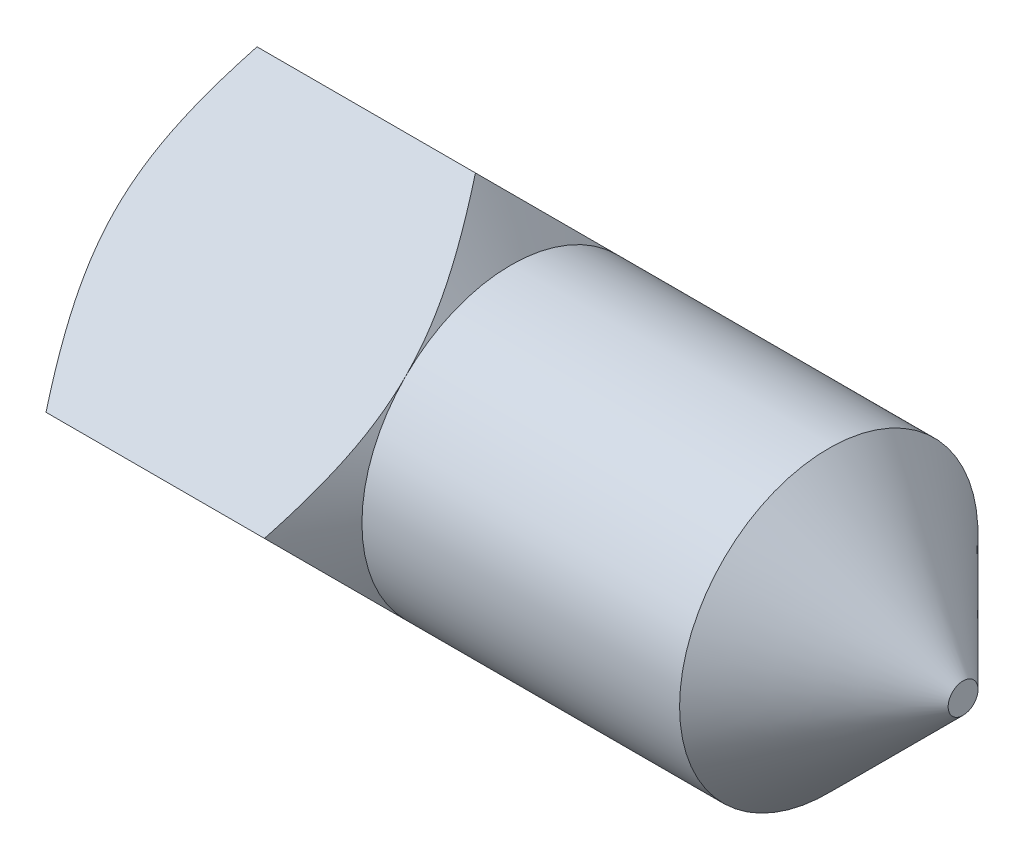
SolidWorks part; units mm, degrees
ref_plane "Front Plane" through (0, 0, 0) normal (0, 0, 1) x (1, 0, 0)
ref_plane "Top Plane" through (0, 0, 0) normal (0, 1, 0) x (1, 0, 0)
ref_plane "Right Plane" through (0, 0, 0) normal (1, 0, 0) x (0, 0, -1)
sketch "BaseHeadSke" plane through (0, 0, 0) normal (1, 0, 0) x (0, 0, -1)
  line L0 (0, 0) -> (14.1701, 0) construction
  line L1 (0, 0) -> (0, 11.9761) construction
  line L2 (0, 2.8284) -> (2.8284, 0)
  line L3 (0, -2.8284) -> (2.8284, 0)
  line L4 (0, 2.8284) -> (-2.8284, 0)
  line L5 (0, -2.8284) -> (-2.8284, 0)
  dimension "D1" = 45
  dimension "Width_flats" = 4
extrude "BaseHead" add sketch "BaseHeadSke" along normal blind 4
sketch "HeadChamferSke" plane through (0, 0, 0) normal (0, 0, 1) x (1, 0, 0)
  line L0 (0, 0) -> (6.1973, 0) construction
  line L1 (2, 2.8284) -> (2, -3.5627) construction
  line L2 (4, 2.8284) -> (0, 2.8284) construction
  line L3 (0, 2.8284) -> (0, 1.9)
  line L4 (0, 2.8284) -> (0.536, 2.8284)
  line L5 (0.536, 2.8284) -> (0, 1.9)
  line L6 (0, 2.8284) -> (0, 0) construction
  line L7 (3.464, 2.8284) -> (4, 1.9)
  line L8 (4, 2.8284) -> (3.464, 2.8284)
  line L9 (4, 2.8284) -> (4, 1.9)
  dimension "D1" = 30
  dimension "Head_chamfer" = 3.8
revolve "HeadChamfer" cut sketch "HeadChamferSke" angle 360 about L0
sketch "BodySke" plane through (0, 0, 0) normal (0, 0, 1) x (1, 0, 0)
  line L0 (0, 0) -> (13.1857, 0) construction
  line L1 (4, -1.9) -> (4, 1.9) construction
  line L2 (4, 0) -> (4, 1.9) construction
  line L3 (3.464, 2) -> (10, 2)
  line L4 (10, 2) -> (10, 0)
  line L5 (4, 1.9) -> (4, 2) construction
  line L6 (3.464, 2) -> (3.464, 0)
  line L7 (3.464, 0) -> (10, 0)
  line L8 (9.3, -3.7301) -> (9.3, 4.8101) construction
  point P9 (3.464, 1.61)
  dimension "Advance" = 0.7
revolve "BaseBody" add sketch "BodySke" angle 360 about L0
cosmetic thread "ThreadCosmetic" [suppressed] parameters "D2"=3.22
sketch "ChamferEndSke" plane through (0, 0, 0) normal (0, 0, 1) x (1, 0, 0)
  line L0 (0, 0) -> (11.9528, 0) construction
  line L1 (10, 2) -> (10, 0.2)
  line L2 (10, 0.2) -> (8.2, 2)
  line L3 (8.2, 2) -> (10, 2)
  line L4 (10, 2) -> (3.9423, 2) construction
  line L5 (10, -2) -> (10, 2) construction
  dimension "D1" = 45
revolve "ChamferEnd" cut sketch "ChamferEndSke" angle 360 about L0
sketch "ThdSchSke" plane through (0, 0, 0) normal (0, 0, 1) x (1, 0, 0)
  line L0 (7.5, 2.4503) -> (7.5, 2)
  line L1 (7.5, 2.4503) -> (7.9503, 2.4503)
  line L2 (7.9503, 2.4503) -> (7.9503, 2)
  line L3 (7.9503, 2) -> (7.7252, 1.61)
  line L4 (7.7252, 1.61) -> (7.5, 2)
  line L5 (0, 0) -> (11.8711, 0) construction
  line L6 (8.2, 2) -> (3.9423, 2) construction
  dimension "D1" = 0.7
revolve "ThreadSchematic" [suppressed] cut sketch "ThdSchSke" angle 360 about L5
pattern_linear "ThdSchPat" [suppressed] count 5 of bodies 105
equation "\"D2@ThreadCosmetic\" = \"Minor_dia@BodySke\""
equation "\"D1@ThdSchSke\" = \"Advance@BodySke\""
equation "\"Advance@ThdSchPat\" = \"Advance@BodySke\""
equation "\"D1@ThdSchPat\" =  int( (  \"Length@BodySke\"  -  ( \"Diameter@BodySke\" - \"End_chamfer@ChamferEndSke\" )  / 2  )  / \"Advance@ThdSchPat\" ) - 1"
